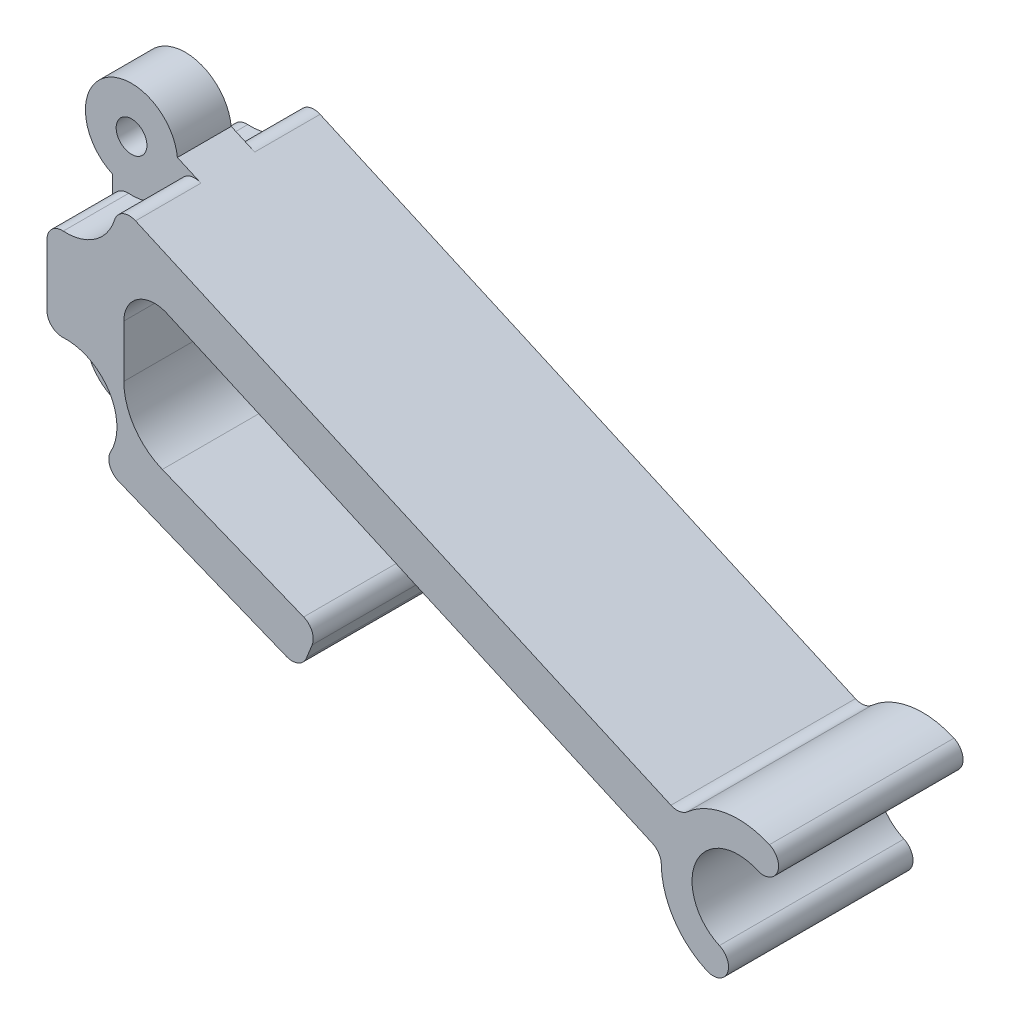
SolidWorks part; units mm, degrees
ref_plane "Front Plane" through (0, 0, 0) normal (0, 0, 1) x (1, 0, 0)
ref_plane "Top Plane" through (0, 0, 0) normal (0, 1, 0) x (1, 0, 0)
ref_plane "Right Plane" through (0, 0, 0) normal (1, 0, 0) x (0, 0, -1)
sketch "Sketch1" plane through (0, 0, 0) normal (0, 0, 1) x (1, 0, 0)
  line L0 (0.3327, 15.1693) -> (0.3327, 22.3049)
  line L2 (4.5662, 25.3457) -> (41.5395, 8.8842)
  line L3 (40.3192, 6.1435) -> (5.3327, 21.7206)
  line L7 (1.5827, 25.0321) -> (1.5827, 12.4421) construction
  line L9 (5.3327, 12.5448) -> (17.9531, 7.4459)
  line L11 (3.4297, 10.0781) -> (16.8292, 4.6643)
  line L12 (16.8292, 4.6643) -> (17.9531, 7.4459)
  line L13 (9.9681, 19.4037) -> (9.9681, 50019.4037) construction
  line L15 (0.3327, 18.7371) -> (2.3545, 18.7371) construction
  line L16 (17.3912, 6.0551) -> (1.5827, 12.4421) construction
  line L17 (45.2867, 5.5738) -> (1.5827, 25.0321) construction
  line L18 (46.9136, 9.228) -> (43.6597, 1.9197) construction
  line L20 (5.3327, 21.7206) -> (5.3327, 12.5448)
  arc A0 (0.3327, 22.3049) -> (4.5662, 25.3457) centre (1.5827, 25.0321) cw
  arc A1 (0.3327, 15.1693) -> (3.4297, 10.0781) centre (1.5827, 12.4421) ccw
  arc A2 (41.5395, 8.8842) -> (47.3204, 10.1416) centre (45.2867, 5.5738) cw
  arc A3 (47.3204, 10.1416) -> (46.5069, 8.3145) centre (46.9136, 9.228) cw
  arc A4 (46.5069, 8.3145) -> (44.0665, 2.8332) centre (45.2867, 5.5738) ccw
  arc A5 (44.0665, 2.8332) -> (43.253, 1.0061) centre (43.6597, 1.9197) cw
  arc A6 (43.253, 1.0061) -> (40.3192, 6.1435) centre (45.2867, 5.5738) cw
  circle A7 centre (1.5827, 25.0321) radius 1
  circle A8 centre (1.5827, 12.4421) radius 1
  dimension "D1" = 3
  dimension "D2" = 2
  dimension "D10" = 5
  dimension "D11" = 3
  dimension "D3" = 12.59
  dimension "D5" = 3
  dimension "D6" = 3
  dimension "D7" = 114
  dimension "D9" = 2.5
  dimension "D12" = 47.84
  dimension "D13" = 17.05
  dimension "D4" = 68
  dimension "D8" = 5
extrude "Boss-Extrude1" add sketch "Sketch1" along normal blind 12
ref_plane "midplane" through (0, 0, 6) normal (0, 0, 1) x (1, 0, 0)
sketch "Sketch2" plane through (0, 0, 12) normal (0, 0, 1) x (1, 0, 0)
  circle A0 centre (1.5827, 25.0321) radius 3.3
  circle A1 centre (1.5827, 12.4421) radius 3.3
  dimension "D1" = 6.6
extrude "Cut-Extrude1" cut sketch "Sketch2" against normal blind 4.25
mirror "Mirror1" about plane through (0, 0, 6) normal (0, 0, 1) of "Cut-Extrude1"
fillet "Fillet1" radius 1 4 edges at (0.3327, 15.4962, 2.125) (0.3327, 15.4962, 9.875) (0.3327, 21.978, 2.125) (0.3327, 21.978, 9.875)
fillet "Fillet2" radius 1 2 edges at (16.8292, 4.6643, 6) (17.9531, 7.4459, 6)
fillet "Fillet3" radius 2 1 edges at (5.3327, 21.7206, 6)
fillet "Fillet6" radius 1 4 edges at (3.7461, 9.9502, 2.125) (3.7461, 9.9502, 9.875) (4.878, 25.2069, 2.125) (4.878, 25.2069, 9.875)
fillet "Fillet7" radius 4 1 edges at (5.3327, 12.5448, 6)
fillet "Fillet8" radius 1 2 edges at (40.3192, 6.1435, 6) (41.5395, 8.8842, 6)
equation "\"axle-diameter\"=2"
equation "\"switch-thickness\"=12"
equation "\"base-width\"=4.0"
equation "\"axle-bushing-radius\"=3"
equation "\"D2@Sketch1\"=\"axle-diameter\""
equation "\"D1@Sketch1\"=\"axle-bushing-radius\""
equation "\"D1@Boss-Extrude1\"=\"switch-thickness\""
equation "\"D5@Sketch1\"=\"arm-width\""
equation "\"D6@Sketch1\"=\"arm-width\""
equation "\"D1@Sketch2\"=\"axle-bushing-radius\"*2.2"
equation "\"D1@Cut-Extrude1\"=\"switch-thickness\"/3+\"clearance\""
equation "\"clearance\"= 0.25"
equation "\"arm-width\"=3.0"
equation "\"min-diameter\"=70"
